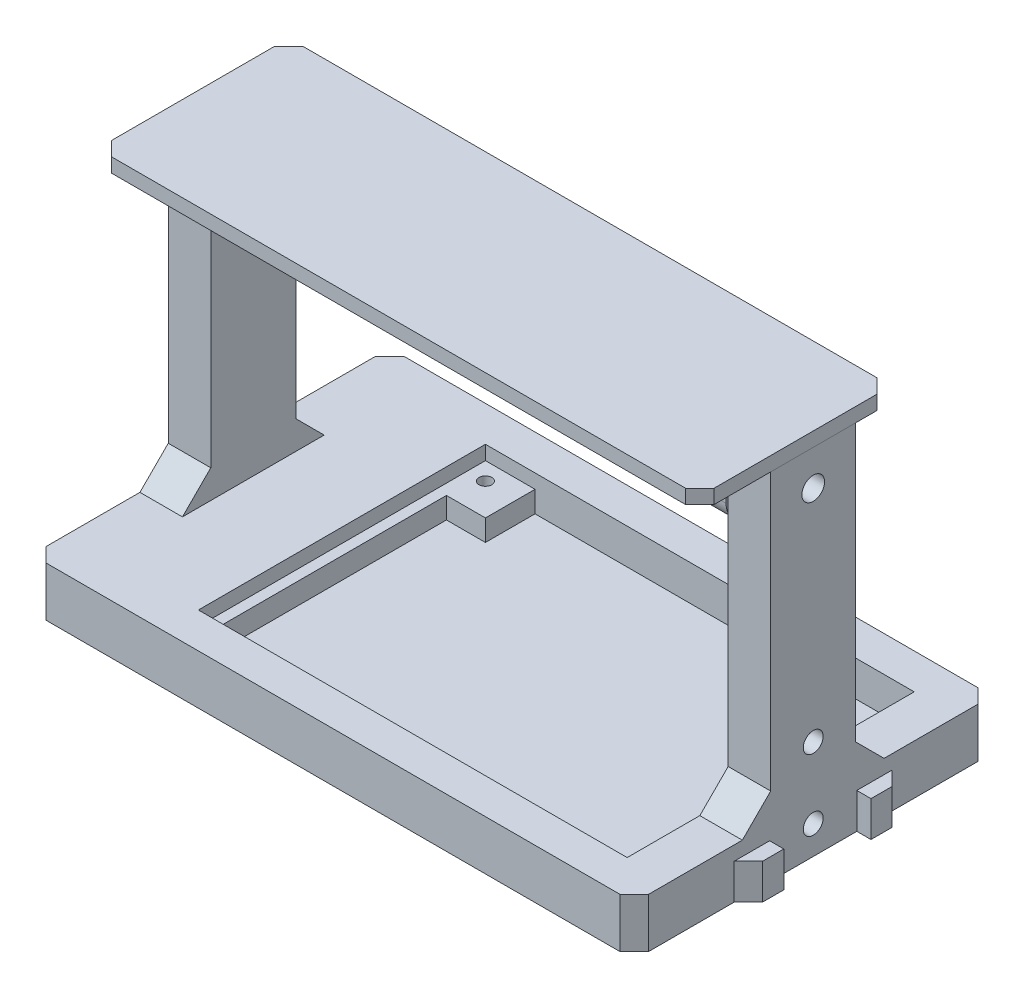
SolidWorks part; units mm, degrees
ref_plane "Piano frontale" through (0, 0, 0) normal (0, 0, 1) x (1, 0, 0)
ref_plane "Piano superiore" through (0, 0, 0) normal (0, 1, 0) x (1, 0, 0)
ref_plane "Piano destro" through (0, 0, 0) normal (1, 0, 0) x (0, 0, -1)
sketch "Schizzo1" plane through (0, 0, 0) normal (0, 1, 0) x (1, 0, 0)
  line L0 (0, 0) -> (36.5, 0) construction
  line L1 (-42.5, -25.25) -> (42.5, -25.25)
  line L2 (-42.5, -25.25) -> (-42.5, 25.25)
  line L3 (-42.5, 25.25) -> (42.5, 25.25)
  line L4 (42.5, -25.25) -> (42.5, 25.25)
  line L5 (-42.5, -25.25) -> (42.5, 25.25) construction
  line L6 (-42.5, 25.25) -> (42.5, -25.25) construction
  line L7 (-24, 20.25) -> (36.5, 20.25)
  line L8 (-24, 20.25) -> (-24, -20.25)
  line L9 (-24, -20.25) -> (36.5, -20.25)
  line L10 (36.5, 20.25) -> (36.5, -20.25)
  point P0 (0, 0)
  dimension "D1" = 85
  dimension "D2" = 6
  dimension "D3" = 60.5
  dimension "D4" = 40.5
  dimension "D5" = 5
extrude "Estrusione-Estrusione1" add sketch "Schizzo1" along normal blind 7
extrude "Estrusione-Estrusione2" add sketch "Schizzo1<3>" along normal blind 2 contours L10 L7 L8 L9 region at (6.25, 0, 0)
sketch "Schizzo1<3>" plane through (0, 0, 0) normal (0, 1, 0) x (1, 0, 0) same geometry as "Schizzo1"
sketch "Schizzo3" plane through (0, 2, 0) normal (0, 1, 0) x (1, 0, 0)
  line L0 (-22.5, 20.25) -> (-22.5, -20.25)
  line L1 (36.5, 20.25) -> (-24, 20.25) construction
  line L2 (-24, -20.25) -> (36.5, -20.25) construction
  line L4 (36.5, -20.25) -> (36.5, 20.25) construction
  line L5 (-24, -20.25) -> (36.5, -20.25) construction
  line L6 (-24, 20.25) -> (36.5, 20.25) construction
  line L7 (-24, 20.25) -> (-24, -20.25) construction
  line L8 (36.5, -20.25) -> (36.5, 20.25)
  line L9 (-24, -20.25) -> (36.5, -20.25)
  line L10 (-24, 20.25) -> (36.5, 20.25)
  line L11 (-24, 20.25) -> (-24, -20.25)
  line L12 (35, 20.25) -> (35, -20.25)
  line M7 (36.5, -20.25) -> (36.5, 20.25)
  line M8 (36.5, 20.25) -> (-24, 20.25)
  line M9 (-24, 20.25) -> (-24, -20.25)
  line M10 (-24, -20.25) -> (36.5, -20.25)
  dimension "D1" = 1.5
  dimension "D2" = 1.5
extrude "Estrusione-Estrusione3" add sketch "Schizzo3" along normal blind 3 contours L0 M8 M9 M10 | L12 L9 M8 M7 region at (-23.25, 2, 0) region at (35.75, 2, 0)
sketch "Schizzo4" plane through (42.5, 0, 0) normal (1, 0, 0) x (0, 0, -1)
  line L0 (-25.25, 7) -> (25.25, 7) construction
  line L1 (-6, 7) -> (6, 7)
  line L2 (-6, 7) -> (-6, 50)
  line L3 (-6, 50) -> (6, 50)
  line L4 (6, 50) -> (6, 7)
  line L5 (0, 0) -> (0, 50) construction
  line L6 (-25.25, 0) -> (25.25, 0) construction
  dimension "D1" = 12
  dimension "D2" = 50
extrude "Estrusione-Estrusione4" add sketch "Schizzo4" against normal up to surface (6 mm away) up to face at (36.5, 6, 0)
extrude "Estrusione-Estrusione5" add sketch "Schizzo4<2>" along normal blind 6 from surface starting at face at (-42.5, 3.5, 0)
sketch "Schizzo4<2>" plane through (42.5, 0, 0) normal (1, 0, 0) x (0, 0, -1) same geometry as "Schizzo4"
sketch "Schizzo5" plane through (42.5, 0, 0) normal (1, 0, 0) x (0, 0, -1)
  line L0 (0, 0) -> (0, 50) construction
  line L1 (-25.25, 0) -> (25.25, 0) construction
  line L2 (6, 50) -> (-6, 50) construction
  circle A0 centre (0, 4) radius 1.4
  circle A1 centre (0, 14) radius 1.4
  dimension "D1" = 2.8
  dimension "D2" = 2.8
  dimension "D3" = 10
  dimension "D4" = 4
extrude "Taglio-Estrusione1" cut sketch "Schizzo5" against normal blind 5.5
mirror "Specchia1" about plane through (0, 0, 0) normal (1, 0, 0) of "Taglio-Estrusione1"
chamfer "Smusso1" distance 4 angle 45 4 edges at (-39.5, 7, -6) (-39.5, 7, 6) (39.5, 7, -6) (39.5, 7, 6)
sketch "Schizzo7" plane through (42.5, 0, 0) normal (1, 0, 0) x (0, 0, -1)
  line L0 (-6.15, 0) -> (-6.15, 5)
  line L1 (-25.25, 0) -> (25.25, 0) construction
  line L2 (-6.15, 5) -> (-9.15, 5)
  line L3 (-9.15, 5) -> (-9.15, 0)
  line L4 (-9.15, 0) -> (-6.15, 0)
  line L5 (0, 0) -> (0, 50) construction
  line L6 (6, 50) -> (-6, 50) construction
  line L7 (9.15, 0) -> (6.15, 0)
  line L8 (9.15, 5) -> (9.15, 0)
  line L9 (6.15, 5) -> (9.15, 5)
  line L10 (6.15, 0) -> (6.15, 5)
  dimension "D1" = 3
  dimension "D2" = 12.3
  dimension "D3" = 5
extrude "Estrusione-Estrusione6" add sketch "Schizzo7" along normal blind 2
mirror "Specchia2" about plane through (0, 0, 0) normal (1, 0, 0) of "Estrusione-Estrusione6"
chamfer "Smusso2" distance 2 angle 45 4 edges at (42.5, 2.5, -9.15) (42.5, 2.5, 9.15) (-42.5, 2.5, -9.15) (-42.5, 2.5, 9.15)
chamfer "Smusso3" distance 2 angle 45 4 edges at (-42.5, 3.5, 25.25) (-42.5, 3.5, -25.25) (42.5, 3.5, 25.25) (42.5, 3.5, -25.25)
sketch "Schizzo8" plane through (36.5, 0, 0) normal (-1, 0, 0) x (0, 0, 1)
  line L0 (0, 0) -> (0, 6.7) construction
  line L1 (-2.5, 6.7) -> (2.5, 6.7)
  line L2 (2.5, 6.7) -> (2.5, 7.7)
  line L3 (2.5, 7.7) -> (-2.5, 7.7)
  line L4 (-2.5, 7.7) -> (-2.5, 6.7)
  line L5 (20.25, 5) -> (-20.25, 5) construction
  line L6 (20.25, 5) -> (-20.25, 5) construction
  dimension "D1" = 1
  dimension "D2" = 5
  dimension "D3" = 1.7
extrude "Estrusione-Estrusione7" add sketch "Schizzo8" along normal blind 1
chamfer "Smusso4" distance 1 angle 45 1 edges at (36.5, 7.7, 0)
sketch "Schizzo9" plane through (0, 2, 0) normal (0, 1, 0) x (1, 0, 0)
  line L0 (-22.5, 13.25) -> (-17, 13.25)
  line L1 (-17, 13.25) -> (-17, 20.25)
  line L2 (-24, 20.25) -> (-24, -20.25) construction
  line L4 (-22.5, -20.25) -> (35, -20.25)
  line L5 (35, -20.25) -> (35, 20.25)
  line L6 (35, 20.25) -> (-22.5, 20.25)
  line L7 (-22.5, 20.25) -> (-22.5, -20.25)
  line L8 (-22.5, -20.25) -> (35, -20.25)
  line L9 (35, -20.25) -> (35, 20.25)
  line L10 (35, 20.25) -> (-22.5, 20.25)
  line L11 (-22.5, 20.25) -> (-22.5, -20.25)
  line M9 (35, 20.25) -> (-22.5, 20.25)
  line M10 (-22.5, 20.25) -> (-22.5, -20.25)
  dimension "D2" = 7
  dimension "D3" = 7
  dimension "D1" = 0
extrude "Estrusione-Estrusione8" add sketch "Schizzo9" along normal up to surface (3 mm away) contours L0 L1 M9 M10 region at (-19.75, 2, -16.75) up to face at (-23.25, 5, 0)
sketch "Schizzo10" plane through (0, 5, 0) normal (0, 1, 0) x (1, 0, 0)
  line L0 (-24, 20.25) -> (-24, -20.25) construction
  line L1 (-17, 20.25) -> (-24, 20.25) construction
  circle A0 centre (-21.5, 17.75) radius 0.9
  dimension "D1" = 1.8
  dimension "D2" = 2.5
  dimension "D3" = 2.5
extrude "Taglio-Estrusione2" cut sketch "Schizzo10" against normal blind 4
sketch "Schizzo11" plane through (42.5, 0, 0) normal (1, 0, 0) x (0, 0, -1)
  line L0 (0, 50) -> (0, 45) construction
  line L1 (6, 50) -> (-6, 50) construction
  circle A0 centre (0, 45) radius 1.6
  dimension "D1" = 3.2
  dimension "D2" = 5
extrude "Taglio-Estrusione3" cut sketch "Schizzo11" against normal through all
sketch "Schizzo13" plane through (0, 50, 0) normal (0, 1, 0) x (1, 0, 0)
  line L0 (-42.5, 23.25) -> (-42.5, 10) construction
  line L1 (-42.5, 11) -> (42.5, 11)
  line L2 (-42.5, 11) -> (-42.5, -16)
  line L3 (-42.5, -16) -> (42.5, -16)
  line L4 (42.5, 11) -> (42.5, -16)
  line L5 (42.5, -23.25) -> (42.5, -10) construction
  line L6 (42.5, 6) -> (36.5, 6) construction
  line L7 (36.5, -6) -> (42.5, -6) construction
  dimension "D1" = 5
  dimension "D2" = 10
extrude "Estrusione-Estrusione10" add sketch "Schizzo13" along normal blind 2 separate body
sketch "Schizzo15" plane through (0, 50, 0) normal (0, -1, 0) x (1, 0, 0)
  line L0 (-36.5, -6) -> (-36.5, 6) construction
  line L1 (-36.5, -6) -> (-36.5, 6) construction
  line L3 (-36.2, 6) -> (-31.2, 6)
  line L4 (-36.2, 6) -> (-36.2, -6)
  line L5 (-36.2, -6) -> (-31.2, -6)
  line L6 (-31.2, 6) -> (-31.2, -6)
  dimension "D1" = 0.3
  dimension "D2" = 5
extrude "Estrusione-Estrusione11" add sketch "Schizzo15" along normal blind 10
mirror "Specchia4" about plane through (0, 0, 0) normal (1, 0, 0) of "Estrusione-Estrusione11"
sketch "Schizzo16" plane through (36.2, 0, 0) normal (1, 0, 0) x (0, 0, -1)
  circle A0 centre (0, 45) radius 1.6 construction
  circle A1 centre (0, 45) radius 1.6 construction
  circle A2 centre (0, 45) radius 1.35
  dimension "D1" = 2.7
extrude "Taglio-Estrusione4" cut sketch "Schizzo16" against normal through all
fillet "Raccordo1" radius 3 4 edges at (33.7, 40, -6) (33.7, 40, 6) (-33.7, 40, -6) (-33.7, 40, 6)
chamfer "Smusso5" distance 2 angle 45 4 edges at (42.5, 51, -11) (42.5, 51, 16) (-42.5, 51, -11) (-42.5, 51, 16)
